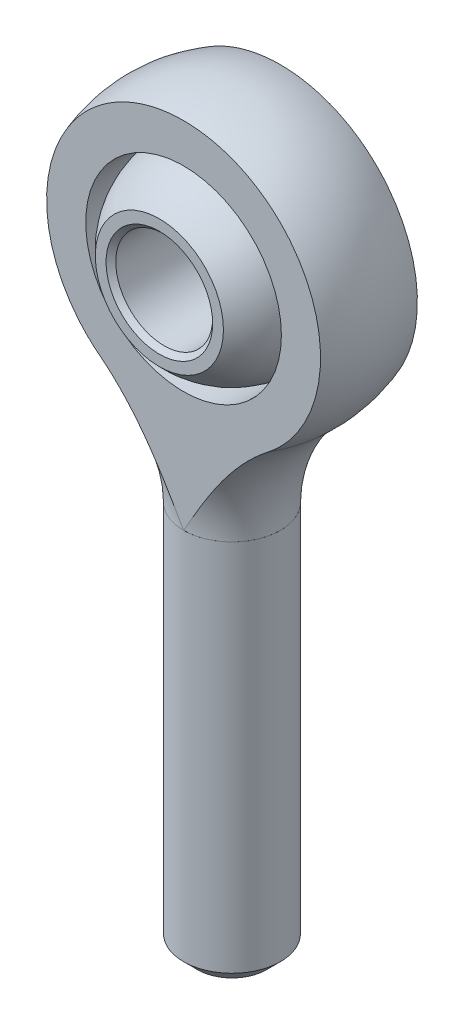
SolidWorks part; units mm, degrees
ref_plane "Front" through (0, 0, 0) normal (0, 0, 1) x (1, 0, 0)
ref_plane "Top" through (0, 0, 0) normal (0, 1, 0) x (1, 0, 0)
ref_plane "Right" through (0, 0, 0) normal (1, 0, 0) x (0, 0, -1)
sketch "Sketch1" plane through (0, 0, 0) normal (0, 0, 1) x (1, 0, 0)
  line L0 (0, 0) -> (0, -25.4)
  line L1 (0, -25.4) -> (3.175, -25.4)
  line L2 (3.175, -25.4) -> (3.175, 0)
  line L3 (3.175, 0) -> (0, 0)
  line L5 (0, 23.8125) -> (0, 0) construction
  line L6 (0, 23.8125) -> (9.525, 23.8125) construction
  line L7 (9.525, 23.8125) -> (9.525, 14.2875) construction
  line L8 (-3.175, -25.4) -> (-3.175, 0) construction
  line L9 (3.2732, -25.3433) -> (3.2732, -26.2501)
  line L10 (3.2732, -26.2501) -> (2.4879, -25.7967)
  line L11 (2.586, -25.8534) -> (2.586, -25.74)
  line L12 (2.4879, -25.7967) -> (3.2732, -25.3433)
  line L13 (3.2241, -25.3717) -> (3.2241, -26.2218)
  line L14 (3.2732, -25.7967) -> (3.175, -25.7967)
  line L15 (3.175, -25.4) -> (3.175, -26.1934)
  line L16 (2.4879, -25.7967) -> (2.586, -25.7967)
  arc A0 (6.3827, 7.2174) -> (0, 23.8125) centre (0, 14.2875) ccw construction
  circle A1 centre (0, 14.2875) radius 3.175 construction
  circle A2 centre (0, 14.2875) radius 6.35 construction
  circle A3 centre (0, 14.2875) radius 6.4135 construction
  arc A4 (3.175, 0) -> (6.3827, 7.2174) centre (12.8984, 0) cw construction
  point P24 (0, 20.6375)
  point P26 (3.175, -25.7967)
  point P28 (3.2241, -25.7967)
  dimension "A" = 6.35
  dimension "Ball Dia" = 12.7
  dimension "B" = 19.05
  dimension "D1" = 12.827
  dimension "D" = 39.6875
  dimension "E" = 25.4
  dimension "Thread Dia" = 6.35
  dimension "D2" = 60
  dimension "Pitch" = 0.9068
  dimension "D4" = 0.1133
sketch "Sketch2" plane through (0, 0, 0) normal (1, 0, 0) x (0, 0, -1)
  line L0 (3.175, 14.2875) -> (-3.175, 14.2875)
  line L1 (3.175, 15.0498) -> (0, 14.2875) construction
  line L2 (3.175, 13.5252) -> (0, 14.2875) construction
  line L6 (4.7625, 14.2875) -> (-4.7625, 14.2875)
  line L7 (0, 11.1125) -> (0, 17.4625)
  line L8 (0, 23.8125) -> (0, 0) construction
  line L9 (0, 17.4625) -> (0, 11.1125) construction
  circle A0 centre (0, 14.2875) radius 6.35
  circle A1 centre (0, 14.2875) radius 9.525
  point P4 (0, 14.2875)
  point P7 (0, 20.6375)
  point P9 (0, 7.9375)
  point P14 (0, 14.2875)
  point P18 (0, 14.2875)
  point P23 (9.525, 14.2875)
  point P25 (-9.525, 14.2875)
  dimension "OAWidth" = 6.35
  dimension "Swivel" = 27
  dimension "BallWidth" = 9.525
sketch "Sketch15" plane through (0, 0, 0) normal (0, 0, 1) x (1, 0, 0)
  line L0 (0, 23.8125) -> (0, 0) construction
  line L1 (9.525, 23.8125) -> (-9.525, 23.8125)
  line L2 (9.525, 23.8125) -> (9.525, 0)
  line L3 (9.525, 0) -> (-9.525, 0)
  line L4 (-9.525, 23.8125) -> (-9.525, 0)
  line L5 (3.175, 0) -> (0, 0) construction
  point P5 (0, 23.8125)
sketch "Sketch14" plane through (0, 0, 0) normal (0, 0, 1) x (1, 0, 0)
  line L1 (0, 0) -> (0, -25.4) construction
  line L2 (0, -25.4) -> (3.175, -25.4) construction
  line L3 (3.175, -25.4) -> (3.175, 0) construction
  line L5 (0, 0) -> (0, -25.4)
  line L6 (0, -25.4) -> (3.175, -25.4)
  line L7 (3.175, -25.4) -> (3.175, 0)
  line L8 (3.175, 0) -> (0, 0) construction
  line L9 (3.175, 0) -> (0, 0)
revolve "Revolve4" add sketch "Sketch14" angle 360 about L0
sketch "Sketch21" plane through (0, 0, 0) normal (0, 0, 1) x (1, 0, 0)
  line L0 (0, 23.8125) -> (0, 0) construction
  line L1 (3.175, 0) -> (0, 0) construction
  line L2 (0, 23.8125) -> (0, 0)
  line L3 (3.175, 0) -> (0, 0)
  arc A0 (6.3827, 7.2174) -> (3.175, 0) centre (12.8984, 0) ccw construction
  arc A1 (6.3827, 7.2174) -> (0, 23.8125) centre (0, 14.2875) ccw construction
  arc A2 (6.3827, 7.2174) -> (3.175, 0) centre (12.8984, 0) ccw
  arc A3 (6.3827, 7.2174) -> (0, 23.8125) centre (0, 14.2875) ccw
revolve "Revolve5" add sketch "Sketch21" angle 360 about L0
sketch "Sketch24" plane through (0, 0, 0) normal (1, 0, 0) x (0, 0, -1)
  line L0 (3.175, 14.2875) -> (3.175, 23.8125)
  line L1 (3.175, 23.8125) -> (9.525, 23.8125)
  line L2 (9.525, 0) -> (9.525, 23.8125)
  line L3 (3.175, 14.2875) -> (3.175, 0.635)
  line L4 (3.175, 0.635) -> (3.175, 0)
  line L5 (3.175, 0) -> (9.525, 0)
  line L6 (0, 23.8125) -> (0, 0) construction
  line L7 (0, 23.8125) -> (0, 0) construction
  line L8 (-3.175, 0) -> (-9.525, 0)
  line L9 (-3.175, 0.635) -> (-3.175, 0)
  line L10 (-3.175, 14.2875) -> (-3.175, 0.635)
  line L11 (-9.525, 0) -> (-9.525, 23.8125)
  line L12 (-3.175, 23.8125) -> (-9.525, 23.8125)
  line L13 (-3.175, 14.2875) -> (-3.175, 23.8125)
  dimension "D1" = 0.635
extrude "Cut-Extrude10" cut sketch "Sketch24" against normal through all both and the other way through all
sketch "Sketch17" plane through (0, 0, 0) normal (0, 0, 1) x (1, 0, 0)
  circle A2 centre (0, 14.2875) radius 6.4135 construction
  circle A3 centre (0, 14.2875) radius 6.4135
extrude "Cut-Extrude9" cut sketch "Sketch17" against normal through all both and the other way through all
sketch "Sketch7" plane through (0, 0, 0) normal (0, 0, 1) x (1, 0, 0)
  line L0 (0, 20.6375) -> (0, 7.9375)
  line L1 (0, 23.8125) -> (0, 0) construction
  line L2 (0, 0) -> (0, 7.9375) construction
  arc A0 (0, 7.9375) -> (0, 20.6375) centre (0, 14.2875) ccw
  circle A1 centre (0, 14.2875) radius 6.35 construction
revolve "Revolve3" add sketch "Sketch7" angle 360 about L2
sketch "Sketch10" plane through (0, 0, 0) normal (0, 0, 1) x (1, 0, 0)
  circle A0 centre (0, 14.2875) radius 3.175 construction
  circle A1 centre (0, 14.2875) radius 3.175
extrude "Cut-Extrude4" cut sketch "Sketch10" against normal through all and the other way through all
sketch "Sketch22" plane through (0, 0, 0) normal (0, 0, 1) x (1, 0, 0)
  line L0 (-9.525, 23.8125) -> (-9.525, 0) construction
  line L1 (9.525, 0) -> (-9.525, 0) construction
  line L2 (9.525, 23.8125) -> (9.525, 0) construction
  line L3 (9.525, 23.8125) -> (-9.525, 23.8125) construction
  line L4 (-9.525, 23.8125) -> (-9.525, 0)
  line L5 (9.525, 0) -> (-9.525, 0)
  line L6 (9.525, 23.8125) -> (9.525, 0)
  line L7 (9.525, 23.8125) -> (-9.525, 23.8125)
extrude "Cut-Extrude7" cut sketch "Sketch22" against normal through all from vertex starting at point (0, 14.2875, -4.7625)
sketch "Sketch23" plane through (0, 0, 0) normal (0, 0, 1) x (1, 0, 0)
  line L0 (-9.525, 23.8125) -> (-9.525, 0) construction
  line L1 (9.525, 0) -> (-9.525, 0) construction
  line L2 (9.525, 23.8125) -> (9.525, 0) construction
  line L3 (9.525, 23.8125) -> (-9.525, 23.8125) construction
  line L4 (-9.525, 23.8125) -> (-9.525, 0)
  line L5 (9.525, 0) -> (-9.525, 0)
  line L6 (9.525, 23.8125) -> (9.525, 0)
  line L7 (9.525, 23.8125) -> (-9.525, 23.8125)
extrude "Cut-Extrude8" cut sketch "Sketch23" along normal through all from vertex starting at point (0, 14.2875, 4.7625)
chamfer "Chamfer1" distance 0.9068 angle 45 1 edges at (-3.175, -25.4, 0)
chamfer "Chamfer2" distance 0.3175 angle 45 2 edges at (3.175, 14.2875, 4.7625) (3.175, 14.2875, -4.7625)
sketch "Sketch18" [suppressed] plane through (0, -25.4, 0) normal (0, -1, 0) x (1, 0, 0)
  circle A0 centre (0, 0) radius 3.175 construction
  circle A1 centre (0, 0) radius 3.175
curve "Helix/Spiral1" [suppressed] pitch 0.9068 height 26.3068 turns 29.0112
sketch "Sketch19" [suppressed] plane through (0, 0, 0) normal (0, 0, 1) x (1, 0, 0)
  line L0 (2.586, -25.8534) -> (2.586, -25.74) construction
  line L1 (2.4879, -25.7967) -> (3.2732, -25.3433) construction
  line L2 (3.2732, -26.2501) -> (2.4879, -25.7967) construction
  line L3 (3.2241, -25.3717) -> (3.2241, -26.2218) construction
  line L4 (2.586, -25.8534) -> (2.586, -25.74)
  line L5 (2.586, -25.74) -> (3.2241, -25.3717)
  line L6 (3.2241, -26.2218) -> (2.586, -25.8534)
  line L7 (3.2241, -25.3717) -> (3.2241, -26.2218)
sweep "Cut-Sweep1" [suppressed] cut profiles "Sketch19" path "Helix/Spiral1"
ref_plane "Plane1" [suppressed] through (0, 0, 0) normal (0, 1, 0) x (1, 0, 0)
sketch "Sketch20" [suppressed] plane through (0, 0, 0) normal (0, 1, 0) x (1, 0, 0)
  circle A0 centre (0, 0) radius 3.175
extrude "Boss-Extrude2" [suppressed] add sketch "Sketch20" against normal through all draft 60
combine bodies "Combine1" [suppressed] operation type add bodies to combine 130 133
sketch "Sketch25" plane through (0, 0, 0) normal (0, 0, 1) x (1, 0, 0)
  line L0 (0, -25.4) -> (0, 14.2875)
  line L1 (-2.2682, -25.4) -> (2.2682, -25.4) construction
  line L2 (0, -25.4) -> (0, -7.62)
  dimension "D1" = 17.78
equation "\"D1@Sketch1\"=\"Ball Dia@Sketch1\"*1.01"
equation "\"D1\"= \"A@Sketch1\" / 20"
equation "\"D3\"= \"E@Sketch1\" + .2"
equation "\"D4@Sketch1\"=\"Pitch@Sketch1\"/8"
equation "\"D1@Chamfer1\"=\"Pitch@Sketch1\""
equation "\"D4@Helix/Spiral1\"=\"Pitch@Sketch1\""
equation "\"D3@Helix/Spiral1\"=\"E@Sketch1\"+\"Pitch@Sketch1\""
equation "\"D1@Chamfer2\"=\"A@Sketch1\"/20"
equation "\"D1@Sketch24\"=(\"OAWidth@Sketch2\"/2)/5"
